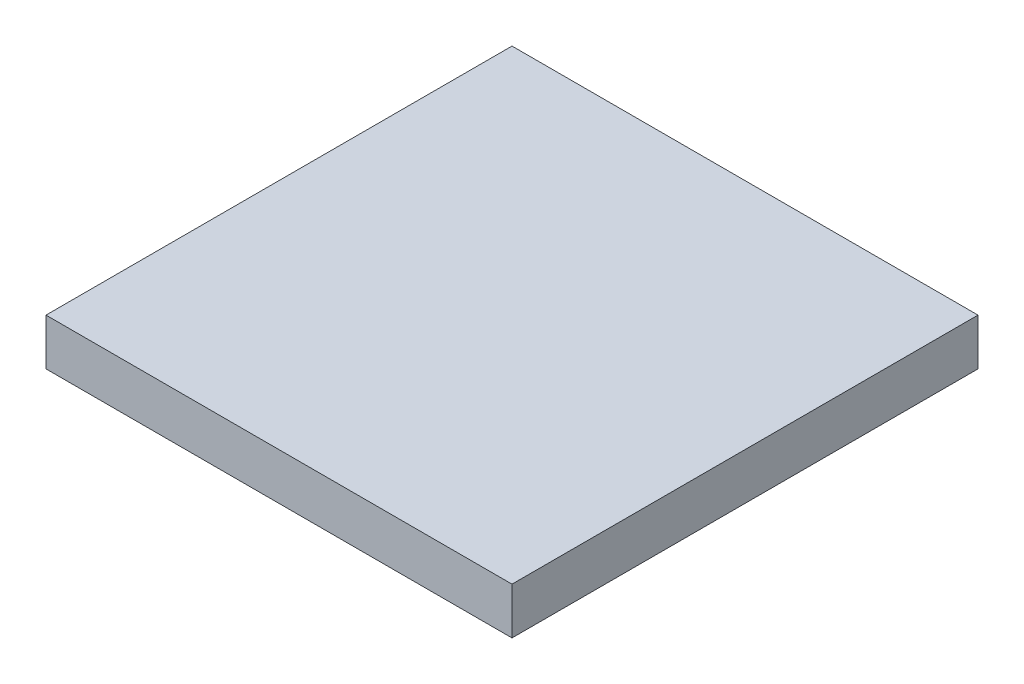
SolidWorks part; units mm, degrees
ref_plane "Front Plane" through (0, 0, 0) normal (0, 0, 1) x (1, 0, 0)
ref_plane "Top Plane" through (0, 0, 0) normal (0, 1, 0) x (1, 0, 0)
ref_plane "Right Plane" through (0, 0, 0) normal (1, 0, 0) x (0, 0, -1)
sketch "Sketch1" plane through (0, 0, 0) normal (0, 1, 0) x (1, 0, 0)
  line L0 (2.5, 12.5) -> (7.5, 17.5)
  line L1 (0, 0) -> (20, 0)
  line L2 (0, 0) -> (0, 20)
  line L3 (0, 20) -> (20, 20)
  line L4 (20, 0) -> (20, 20)
  line L5 (0, 20) -> (2.5, 20)
  line L6 (0, 20) -> (0, 17.5)
  line L7 (0, 17.5) -> (2.5, 17.5)
  line L8 (2.5, 20) -> (2.5, 17.5)
  line L9 (1, 1) -> (19, 1)
  line L10 (1, 1) -> (1, 19)
  line L11 (1, 19) -> (19, 19)
  line L12 (19, 1) -> (19, 19)
  line L13 (1, 1) -> (19, 19) construction
  line L14 (1, 19) -> (19, 1) construction
  circle A0 centre (2.5, 17.5) radius 1.5
  circle A1 centre (7.5, 17.5) radius 1.5
  circle A2 centre (12.5, 17.5) radius 1.5
  circle A3 centre (17.5, 17.5) radius 1.5
  circle A4 centre (2.5, 12.5) radius 1.5
  circle A5 centre (7.5, 12.5) radius 1.5
  circle A6 centre (12.5, 12.5) radius 1.5
  circle A7 centre (17.5, 12.5) radius 1.5
  circle A8 centre (2.5, 7.5) radius 1.5
  circle A9 centre (7.5, 7.5) radius 1.5
  circle A10 centre (12.5, 7.5) radius 1.5
  circle A11 centre (17.5, 7.5) radius 1.5
  circle A12 centre (2.5, 2.5) radius 1.5
  circle A13 centre (7.5, 2.5) radius 1.5
  circle A14 centre (12.5, 2.5) radius 1.5
  circle A15 centre (17.5, 2.5) radius 1.5
  circle A16 centre (5, 15) radius 2.0355
  circle A17 centre (10, 15) radius 2.0355
  circle A18 centre (15, 15) radius 2.0355
  circle A19 centre (10, 10) radius 2.0355
  circle A20 centre (15, 10) radius 2.0355
  circle A21 centre (10, 5) radius 2.0355
  circle A22 centre (15, 5) radius 2.0355
  circle A23 centre (5, 10) radius 2.0355
  circle A24 centre (5, 5) radius 2.0355
  circle A25 centre (5, 15) radius 1.5
  circle A26 centre (10, 15) radius 1.5
  circle A27 centre (15, 15) radius 1.5
  circle A28 centre (10, 10) radius 1.5
  circle A29 centre (15, 10) radius 1.5
  circle A30 centre (10, 5) radius 1.5
  circle A31 centre (15, 5) radius 1.5
  circle A32 centre (5, 10) radius 1.5
  circle A33 centre (5, 5) radius 1.5
  point P8 (10, 10)
  point P13 (10, 19)
  point P14 (10, 20)
  point P15 (1, 10)
  point P16 (0, 10)
  dimension "D8" = 3
  dimension "D1" = 20
  dimension "D2" = 2.5
  dimension "D3" = 1
  dimension "D4" = 4
  dimension "D5" = 4
  dimension "D6" = 3
  dimension "D7" = 3
  dimension "D9" = 3
  dimension "D10" = 3
extrude "Boss-Extrude1" add sketch "Sketch1" against normal blind 1 contours L12 L9 L10 L7 L2 L1 L4 L3 L8 L11 | A24 A33 | A23 A32 | A25 L0 A16 | A25 L0 A16 | A21 A30 | A22 A31 | A18 A27 | A20 A29 | A19 A28 | A17 A26 | L10 L11 L8 L3 L2 L7 region at (3.0136, 0, -15) region at (3.7847, 0, -13.7153) region at (0.7172, 0, -10) region at (5, 0, -11.978) region at (0.9688, 0, -19.0313) region at (8.022, 0, -15) region at (5, 0, -6.978) region at (10, 0, -11.978) region at (13.022, 0, -15) region at (10, 0, -6.978) region at (15, 0, -11.978) region at (15, 0, -6.978)
extrude "Boss-Extrude2" add sketch "Sketch1<3>" along normal blind 1 contours L2 L1 L4 L3
sketch "Sketch1<3>" plane through (0, 0, 0) normal (0, 1, 0) x (1, 0, 0) same geometry as "Sketch1"
